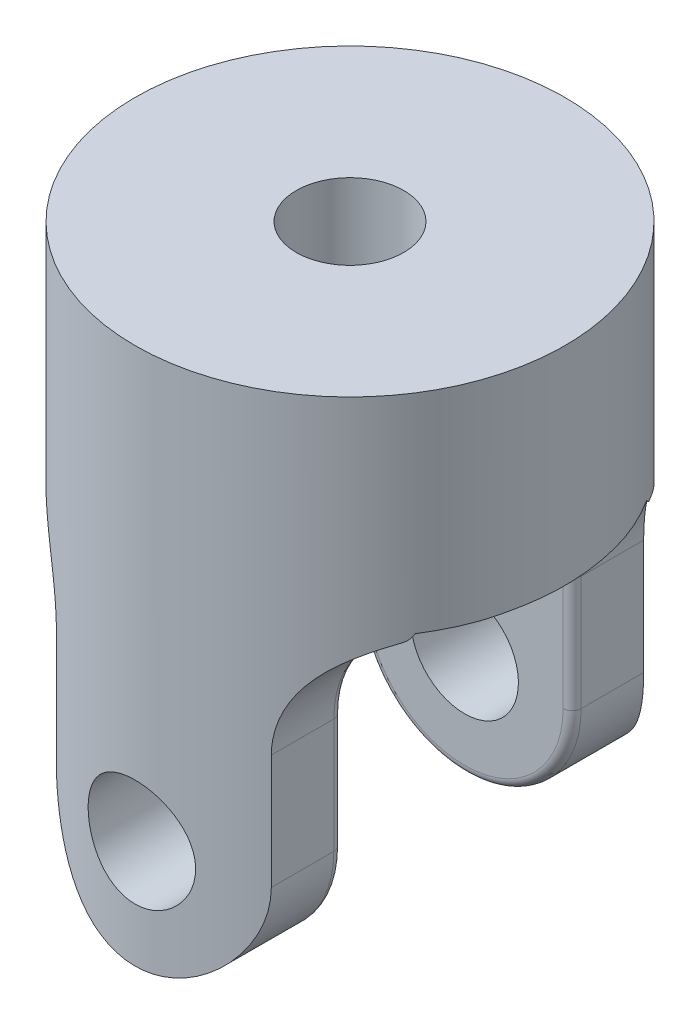
SolidWorks part; units mm, degrees
note: '?' marks a value the reader was unsure of.
ref_plane "Front" through (0, 0, 0) normal (0, 0, 1) x (1, 0, 0)
ref_plane "Top" through (0, 0, 0) normal (0, 1, 0) x (-1, 0, 0)
ref_plane "Right" through (0, 0, 0) normal (1, 0, 0) x (0, 0, -1)
sketch "Sketch1" plane through (0, 0, 0) normal (0, 1, 0) x (-1, 0, 0)
  circle A0 centre (0, 0) radius 19.05
  dimension "D1" = 38.1
extrude "Base-Extrude" add sketch "Sketch1" along normal blind 47.625
sketch "Sketch2" plane through (0, 0, 0) normal (0, 0, 1) x (1, 0, 0)
  line L0 (0, 0) -> (0, 23.7435) construction
  line L1 (9.525, 9.525) -> (9.525, 19.685)
  line L2 (-9.525, 9.525) -> (-9.525, 19.685)
  line L3 (19.05, 29.21) -> (19.05, -1.3662)
  line L4 (19.05, -1.3662) -> (-19.05, -1.3662)
  line L5 (-19.05, -1.3662) -> (-19.05, 29.21)
  line L6 (19.05, 0) -> (-19.05, 0) construction
  arc A0 (-9.525, 9.525) -> (9.525, 9.525) centre (0, 9.525) ccw
  arc A1 (9.525, 19.685) -> (19.05, 29.21) centre (19.05, 19.685) cw
  arc A2 (-9.525, 19.685) -> (-19.05, 29.21) centre (-19.05, 19.685) ccw
  dimension "D3" = 9.525
  dimension "D1" = 38.1
  dimension "D2" = 19.05
  dimension "D4" = 29.21
extrude "Cut-Extrude1" cut sketch "Sketch2" against normal through all and the other way through all
sketch "Sketch8" plane through (0, 0, 0) normal (1, 0, 0) x (0, 0, -1)
  line L0 (-10.16, -7.4553) -> (10.16, -7.4553)
  line L1 (-10.16, -7.4553) -> (-10.16, 29.1452)
  line L2 (10.16, 29.1452) -> (-10.16, 29.1452)
  line L3 (10.16, 29.1452) -> (10.16, -7.4553)
  point P4 (0, 0)
  dimension "D1" = 10.16
  dimension "D2" = 20.32
extrude "Cut-Extrude5" cut sketch "Sketch8" against normal through all and the other way blind 47.625
fillet "Fillet1" radius 0.8001 16 edges at (0, 0, -10.16) (0, 0, 10.16) (12.2929, 26.3982, 14.5529) (-12.2929, 26.3982, 14.5529) (9.525, 14.605, 10.16) (11.3465, 25.287, 10.16) (11.3465, 25.287, -10.16) (9.525, 14.605, -10.16) (16.1145, 28.9458, 10.16) (-9.525, 14.605, 10.16) (-11.3465, 25.287, 10.16) (-16.1145, 28.9458, 10.16) (16.1145, 28.9458, -10.16) (-16.1145, 28.9458, -10.16) (-11.3465, 25.287, -10.16) (-9.525, 14.605, -10.16)
sketch "Sketch11" plane through (0, 0, 0) normal (0, 0, 1) x (1, 0, 0)
  circle A0 centre (0, 9.525) radius 4.7625
  dimension "D1" = 9.525
extrude "Cut-Extrude6" cut sketch "Sketch11" against normal through all and the other way through all
sketch "Sketch12"
  circle A0 centre (0, 0) radius 4.7625
  dimension "D1" = 9.525
extrude "Cut-Extrude7" cut sketch "Sketch12" against normal through all
ref_axis "Axis1" through (0, 97.625, 0) along (0, -1, 0)?
